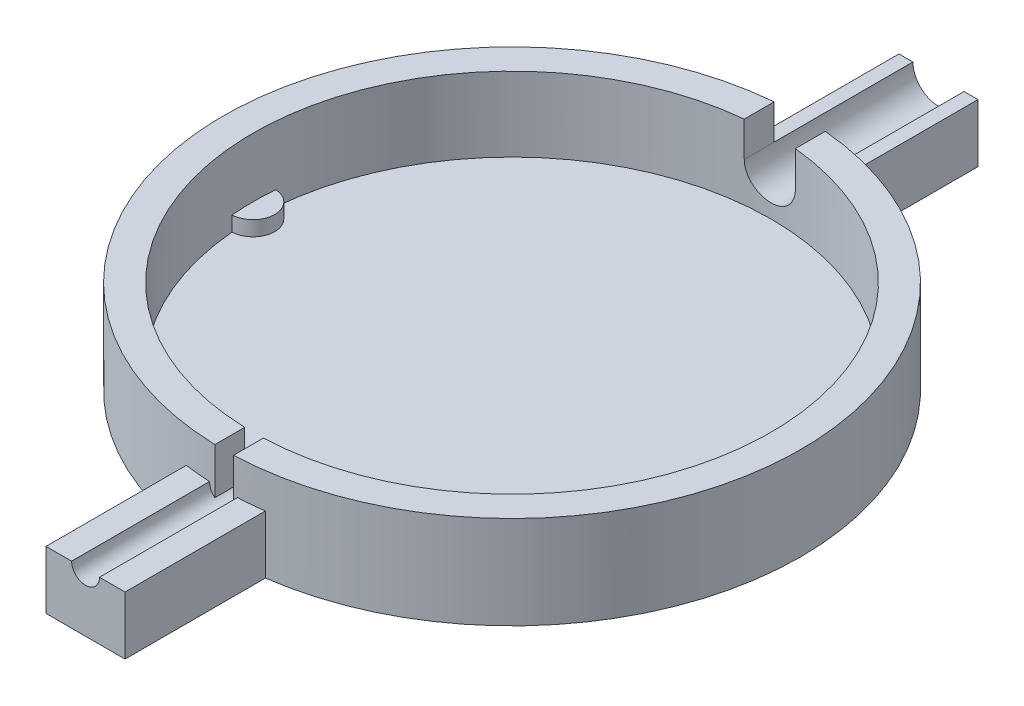
SolidWorks part; units mm, degrees
ref_plane "Front Plane" through (0, 0, 0) normal (0, 0, 1) x (1, 0, 0)
ref_plane "Top Plane" through (0, 0, 0) normal (0, 1, 0) x (1, 0, 0)
ref_plane "Right Plane" through (0, 0, 0) normal (1, 0, 0) x (0, 0, -1)
sketch "Sketch1" plane through (0, 0, 0) normal (0, 1, 0) x (1, 0, 0)
  circle A0 centre (0, 0) radius 31.06
  dimension "D1" = 62.12
extrude "Boss-Extrude1" add sketch "Sketch1" along normal blind 10
sketch "Sketch2" plane through (0, 10, 0) normal (0, 1, 0) x (1, 0, 0)
  circle A0 centre (0, 0) radius 27.86
  circle A1 centre (0, 0) radius 31.06 construction
  circle A2 centre (0, 0) radius 31.06
  dimension "D1" = 3.2
extrude "Cut-Extrude1" cut sketch "Sketch2" against normal blind 8 contours A0 region at (0, 10, 0)
sketch "Sketch3" plane through (0, 2, 0) normal (0, 1, 0) x (1, 0, 0)
  arc A0 (-27.7609, -2.3479) -> (-27.7609, 2.3479) centre (-27.86, 0) ccw
  circle A1 centre (0, 0) radius 27.86 construction
  arc A2 (27.7609, 2.3479) -> (27.7609, -2.3479) centre (27.86, 0) ccw
  arc A3 (27.7609, -2.3479) -> (27.7609, 2.3479) centre (0, 0) ccw
  arc A4 (-27.7609, 2.3479) -> (-27.7609, -2.3479) centre (0, 0) ccw
  dimension "D1" = 4.7
  dimension "D2" = 4.7
extrude "Boss-Extrude2" add sketch "Sketch3" along normal blind 1.6
sketch "Sketch4" plane through (0, 0, 0) normal (0, 0, 1) x (1, 0, 0)
  line L0 (27.7609, 2) -> (-27.7609, 2) construction
  line L1 (27.7609, 2) -> (-27.7609, 2)
  line L2 (0, 0) -> (0, 4.7714)
  line L3 (27.86, 10) -> (-27.86, 10) construction
  line L4 (27.86, 10) -> (-27.86, 10)
  line L5 (-2.75, 6.25) -> (-2.75, 10)
  line L6 (2.75, 6.25) -> (2.75, 10)
  circle A0 centre (0, 6.25) radius 2.75
  dimension "D1" = 5.5
  dimension "D2" = 4.25
extrude "Cut-Extrude2" cut sketch "Sketch4" against normal through all contours A0 L6 L4 L5 | A0 region at (0, 9.0865, 0)
sketch "Sketch5" plane through (0, 0, 0) normal (0, 0, 1) x (1, 0, 0)
  line L0 (27.86, 10) -> (-27.86, 10) construction
  line L1 (1.0982, 3.999) -> (-0.9018, 3.999)
  line L2 (1.0982, 3.999) -> (1.0982, 10)
  line L3 (1.0982, 5.999) -> (-0.9018, 5.999)
  line L4 (-0.9018, 3.999) -> (-0.9018, 10)
  line L5 (1.0982, 3.999) -> (-0.9018, 5.999) construction
  line L6 (1.0982, 5.999) -> (-0.9018, 3.999) construction
  line L7 (1.0982, 10) -> (-0.9018, 10)
  point P0 (0.0982, 4.999)
  dimension "D1" = 2
  dimension "D2" = 2
  dimension "D3" = 5
extrude "Cut-Extrude3" cut sketch "Sketch5" along normal through all contours L2 L7 L4 L1
ref_plane "Plane1" through (0, 0, -27.86) normal (0, 0, 1) x (1, 0, 0)
sketch "Sketch6" plane through (0, 0, -27.86) normal (0, 0, 1) x (1, 0, 0)
  line L0 (-31.06, 0) -> (31.06, 0) construction
  line L1 (-4.25, 0) -> (4.25, 0)
  line L2 (4.25, 6.25) -> (4.25, 0)
  line L3 (-4.25, 6.25) -> (-4.25, 0)
  line L4 (-4.25, 6.25) -> (-2.75, 6.25)
  line L5 (-2.75, 6.25) -> (-2.7454, 6.232)
  line L6 (2.75, 6.25) -> (4.25, 6.25)
  arc A0 (-2.75, 6.25) -> (2.75, 6.25) centre (0, 6.25) ccw construction
  arc A1 (-2.75, 6.25) -> (2.75, 6.25) centre (0, 6.25) ccw
extrude "Boss-Extrude3" add sketch "Sketch6" against normal blind 18 contours A1 L6 L2 L1 L3 L4
ref_plane "Plane2" through (0, 0, 27.86) normal (0, 0, -1) x (-1, 0, 0)
sketch "Sketch7" plane through (0, 0, 27.86) normal (0, 0, -1) x (-1, 0, 0)
  line L5 (4.25, 6.25) -> (2.75, 6.25)
  line L6 (-2.75, 6.25) -> (-4.25, 6.25)
  line L7 (-4.25, 6.25) -> (-4.25, 0)
  line L8 (-4.25, 0) -> (4.25, 0)
  line L9 (4.25, 0) -> (4.25, 6.25)
  line L10 (4.25, 6.25) -> (1.5, 6.25)
  line L11 (-1.5, 6.25) -> (-4.25, 6.25)
  line L12 (-4.25, 6.25) -> (-4.25, 0)
  line L13 (-4.25, 0) -> (4.25, 0)
  line L14 (4.25, 0) -> (4.25, 6.25)
  arc A0 (-1.5, 6.25) -> (1.5, 6.25) centre (0, 6.25) ccw
  arc A1 (-2.75, 6.25) -> (2.75, 6.25) centre (0, 6.25) ccw
  dimension "D2" = 3
  dimension "D1" = 0
extrude "Boss-Extrude4" add sketch "Sketch7" against normal blind 18
